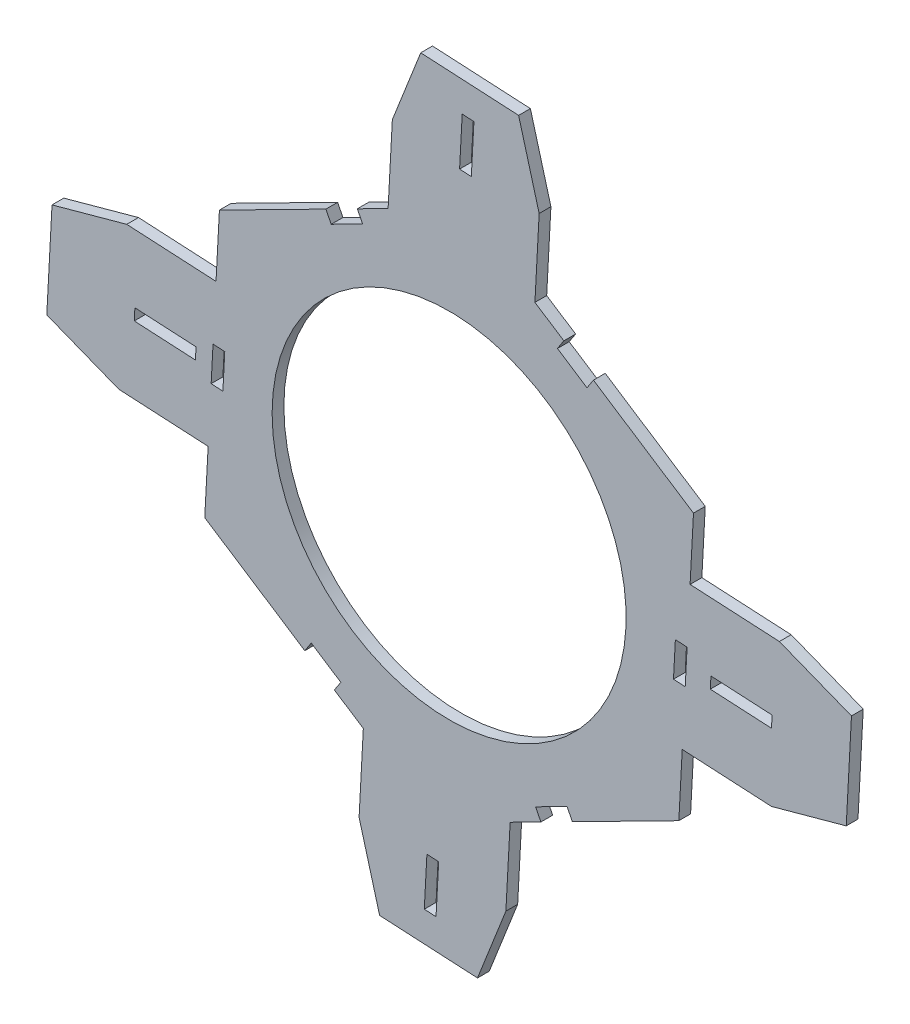
SolidWorks part; units mm, degrees
ref_plane "Front Plane" through (0, 0, 0) normal (0, 0, 1) x (1, 0, 0)
ref_plane "Top Plane" through (0, 0, 0) normal (0, 1, 0) x (1, 0, 0)
ref_plane "Right Plane" through (0, 0, 0) normal (1, 0, 0) x (0, 0, -1)
sketch "Sketch1" plane through (0, 0, 0) normal (0, 0, 1) x (1, 0, 0)
  line L0 (90.4284, 31.6568) -> (86.6282, -39.2725) construction
  line L1 (81.6815, 46.4334) -> (100.7042, 45.4142)
  line L2 (77.4111, -33.2715) -> (76.3525, -53.0299)
  line L3 (96.4338, -34.2907) -> (95.3752, -54.0491)
  line L4 (88.5283, -3.8078) -> (142.4373, -6.6961) construction
  line L5 (76.3525, -53.0299) -> (95.3752, -54.0491)
  line L6 (99.6456, 25.6558) -> (100.7042, 45.4142)
  line L7 (80.6228, 26.675) -> (81.6815, 46.4334)
  line L8 (72.5587, 22.578) -> (58.7651, 15.57)
  line L9 (72.5587, 22.578) -> (73.249, 21.2193)
  line L10 (73.249, 21.2193) -> (77.3251, 23.2902)
  line L11 (76.6348, 24.6489) -> (77.3251, 23.2902)
  line L12 (58.7651, 15.57) -> (58.3246, 7.3491)
  line L13 (140.8308, 2.9286) -> (139.8116, -16.0941)
  line L14 (58.3246, 7.3491) -> (37.245, 8.4785)
  line L15 (57.3055, -11.6736) -> (36.2258, -10.5442)
  line L16 (57.9374, 0.1204) -> (57.6927, -4.445)
  line L17 (37.245, 8.4785) -> (36.2258, -10.5442)
  line L18 (118.732, -14.9647) -> (139.8116, -16.0941)
  line L19 (119.7512, 4.058) -> (140.8308, 2.9286)
  line L20 (119.1193, -7.7361) -> (119.3639, -3.1706)
  line L36 (57.815, -2.1623) -> (59.3369, -2.2438) construction
  line L37 (57.6927, -4.445) -> (59.2146, -4.5265)
  line L38 (57.9374, 0.1204) -> (59.4592, 0.0389)
  line L39 (80.6228, 26.675) -> (76.6348, 24.6489)
  line L40 (59.2146, -4.5265) -> (59.4592, 0.0389)
  line L41 (57.3055, -11.6736) -> (56.865, -19.8946)
  line L46 (103.3943, 23.2152) -> (99.6456, 25.6558)
  line L47 (103.3943, 23.2152) -> (102.5628, 21.938)
  line L48 (102.5628, 21.938) -> (106.3943, 19.4434)
  line L49 (107.2258, 20.7206) -> (106.3943, 19.4434)
  line L50 (120.1916, 12.279) -> (107.2258, 20.7206)
  line L51 (119.7512, 4.058) -> (120.1916, 12.279)
  line L52 (119.3639, -3.1706) -> (117.8421, -3.0891)
  line L53 (117.8421, -3.0891) -> (117.5975, -7.6546)
  line L54 (119.1193, -7.7361) -> (117.5975, -7.6546)
  line L55 (118.2915, -23.1857) -> (118.732, -14.9647)
  line L56 (104.4979, -30.1936) -> (118.2915, -23.1857)
  line L57 (104.4979, -30.1936) -> (103.8076, -28.8349)
  line L58 (103.8076, -28.8349) -> (99.7315, -30.9058)
  line L59 (100.4218, -32.2645) -> (99.7315, -30.9058)
  line L60 (96.4338, -34.2907) -> (100.4218, -32.2645)
  line L61 (73.6624, -30.8308) -> (77.4111, -33.2715)
  line L62 (73.6624, -30.8308) -> (74.4939, -29.5536)
  line L63 (74.4939, -29.5536) -> (70.6624, -27.0591)
  line L64 (69.8309, -28.3362) -> (70.6624, -27.0591)
  line L65 (56.865, -19.8946) -> (69.8309, -28.3362)
  circle A0 centre (88.5283, -3.8078) radius 22.9363
  dimension "D2" = 51.8672
  dimension "D1" = 49.803
extrude "Boss-Extrude1" add sketch "Sketch1" along normal blind 1.524 contours L41 L65 L64 L63 L62 L61 L60 L59 L58 L57 L56 L55 L54 L53 L52 L51 L50 L49 L48 L47 L46 L39 L11 L10 L9 L8 L12 L38 L40 L37 region at (91.1152, 44.4754, 0)
chamfer "Chamfer1" distance 9.525 distance2 3.175 4 edges at (37.245, 8.4785, 0.762) (100.7042, 45.4142, 0.762) (139.8116, -16.0941, 0.762) (76.3525, -53.0299, 0.762) first distance on face at (47.7848, 7.9138, 0.762) first distance on face at (100.1749, 35.535, 0.762) first distance on face at (129.2718, -15.5294, 0.762) first distance on face at (76.8818, -43.1507, 0.762)
chamfer "Chamfer2" distance 3.175 distance2 9.525 4 edges at (81.6815, 46.4334, 0.762) (140.8308, 2.9286, 0.762) (95.3752, -54.0491, 0.762) (36.2258, -10.5442, 0.762) first distance on face at (89.6076, 46.0088, 0.762) first distance on face at (140.4062, -4.9975, 0.762) first distance on face at (87.449, -53.6244, 0.762) first distance on face at (36.6505, -2.6181, 0.762)
sketch "Sketch4" plane through (0, 0, 1.524) normal (0, 0, 1) x (1, 0, 0)
  line L0 (80.6228, 26.675) -> (99.6456, 25.6558) construction
  line L1 (90.1342, 26.1654) -> (90.6445, 35.6904) construction
  line L2 (119.7512, 4.058) -> (118.732, -14.9647) construction
  line L3 (96.4338, -34.2907) -> (77.4111, -33.2715) construction
  line L4 (57.3055, -11.6736) -> (58.3246, 7.3491) construction
  line L5 (57.815, -2.1623) -> (55.6975, -2.0488) construction
  line L6 (86.9224, -33.7811) -> (86.4121, -43.3061) construction
  line L7 (119.2416, -5.4534) -> (122.412, -5.6232) construction
  line L8 (90.6445, 35.6904) -> (90.9843, 42.0313) construction
  line L9 (55.6975, -2.0488) -> (47.7714, -1.6242) construction
  line L10 (86.4121, -43.3061) -> (86.0724, -49.647) construction
  line L11 (91.4054, 35.6497) -> (91.7452, 41.9906)
  line L12 (122.412, -5.6232) -> (130.3382, -6.0479) construction
  line L13 (122.3713, -6.3841) -> (130.2974, -6.8088)
  line L14 (85.6512, -43.2653) -> (85.3115, -49.6062)
  line L15 (55.7383, -1.2879) -> (47.8122, -0.8633)
  line L16 (89.8836, 35.7312) -> (90.2234, 42.0721)
  line L17 (122.4528, -4.8623) -> (130.3789, -5.287)
  line L18 (87.173, -43.3468) -> (86.8333, -49.6877)
  line L19 (55.6568, -2.8097) -> (47.7306, -2.3851)
  line L20 (91.4054, 35.6497) -> (89.8836, 35.7312)
  line L21 (91.7452, 41.9906) -> (90.2234, 42.0721)
  line L22 (122.3713, -6.3841) -> (122.4528, -4.8623)
  line L23 (130.2974, -6.8088) -> (130.3789, -5.287)
  line L24 (85.6512, -43.2653) -> (87.173, -43.3468)
  line L25 (85.3115, -49.6062) -> (86.8333, -49.6877)
  line L26 (55.7383, -1.2879) -> (55.6568, -2.8097)
  line L27 (47.8122, -0.8633) -> (47.7306, -2.3851)
  dimension "D1" = 9.525
  dimension "D2" = 0.762
  dimension "D4" = 9.525
  dimension "D5" = 6.35
  dimension "D6" = 6.35
  dimension "D3" = 0.762
extrude "Cut-Extrude1" cut sketch "Sketch4" against normal blind 2.54
